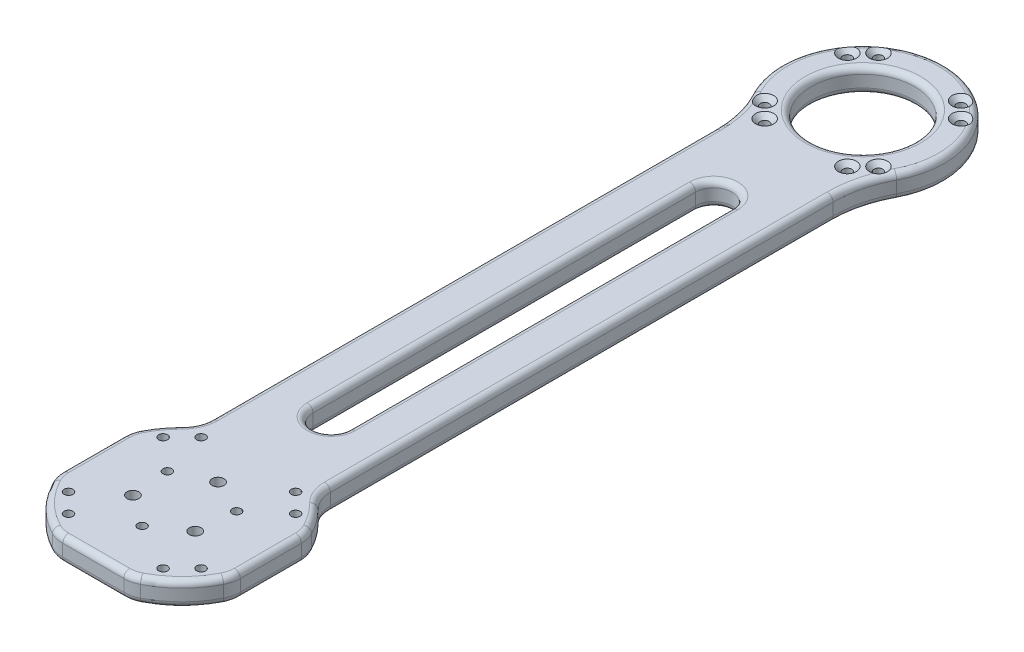
SolidWorks part; units mm, degrees
ref_plane "前视基准面" through (0, 0, 0) normal (0, 0, 1) x (1, 0, 0)
ref_plane "上视基准面" through (0, 0, 0) normal (0, 1, 0) x (1, 0, 0)
ref_plane "右视基准面" through (0, 0, 0) normal (1, 0, 0) x (0, 0, -1)
sketch "草图1" plane through (0, 0, 0) normal (0, 1, 0) x (1, 0, 0)
  line L0 (0, -31.6456) -> (0, -164.4547) construction
  line L2 (-30, 145) -> (-30, -145) construction
  line L3 (-30, -145) -> (30, -145) construction
  line L4 (30, 145) -> (30, -145) construction
  line L5 (-30, 145) -> (30, -145) construction
  line L6 (-30, -145) -> (30, 145) construction
  line L7 (-30, -85) -> (30, -85) construction
  line L8 (-30, -85) -> (-30, -145) construction
  line L9 (-30, -145) -> (30, -145) construction
  line L10 (30, -85) -> (30, -145) construction
  line L11 (-30, -85) -> (30, -145) construction
  line L12 (-30, -145) -> (30, -85) construction
  line L13 (-20, -84.896) -> (-20, 84.896)
  line L14 (-30, -104.6922) -> (-30, -125.3078)
  line L15 (-10.3078, -145) -> (10.3078, -145)
  line L16 (30, -104.6922) -> (30, -125.3078)
  line L17 (20, -84.896) -> (20, 84.896)
  line L18 (0, 0) -> (75.3378, 0) construction
  line L19 (0, -115) -> (-15.9693, -92.6118) construction
  line L20 (15.9693, -92.6118) -> (0, -115) construction
  line L21 (-30, 145) -> (30, 145) construction
  line L22 (0, 115) -> (39.9726, 115) construction
  line L23 (-19.2142, 128.9599) -> (0, 115) construction
  line L24 (-13.9599, 134.2142) -> (0, 115) construction
  circle A0 centre (0, -115) radius 32.5 construction
  arc A1 (-22.9412, -91.9793) -> (-28.8889, -100.111) centre (0, -115) ccw
  arc A2 (-28.8889, -129.889) -> (-14.889, -143.8889) centre (0, -115) ccw
  arc A3 (14.889, -143.8889) -> (28.8889, -129.889) centre (0, -115) ccw
  arc A4 (22.9412, -91.9793) -> (28.8889, -100.111) centre (0, -115) cw
  circle A5 centre (0, -115) radius 27.5 construction
  circle A6 centre (-15.9693, -92.6118) radius 1.5
  circle A8 centre (15.9693, -92.6118) radius 1.5
  circle A9 centre (-22.3882, -130.9693) radius 1.5
  circle A10 centre (-22.3882, -99.0307) radius 1.5
  circle A11 centre (-15.9693, -137.3882) radius 1.5
  circle A12 centre (15.9693, -137.3882) radius 1.5
  circle A13 centre (22.3882, -130.9693) radius 1.5
  circle A14 centre (22.3882, -99.0307) radius 1.5
  arc A15 (20, -84.896) -> (22.9412, -91.9793) centre (30, -84.896) ccw
  arc A16 (30, -104.6922) -> (28.8889, -100.111) centre (20, -104.6922) ccw
  arc A17 (28.8889, -129.889) -> (30, -125.3078) centre (20, -125.3078) ccw
  arc A18 (10.3078, -145) -> (14.889, -143.8889) centre (10.3078, -135) ccw
  arc A19 (-14.889, -143.8889) -> (-10.3078, -145) centre (-10.3078, -135) ccw
  arc A20 (-30, -125.3078) -> (-28.8889, -129.889) centre (-20, -125.3078) ccw
  arc A21 (-28.8889, -100.111) -> (-30, -104.6922) centre (-20, -104.6922) ccw
  arc A22 (-20, -84.896) -> (-22.9412, -91.9793) centre (-30, -84.896) cw
  circle A23 centre (0, -115) radius 13.5 construction
  circle A24 centre (0, -115) radius 12.15 construction
  circle A25 centre (0, -102.85) radius 2
  circle A27 centre (10.5222, -121.075) radius 2
  circle A28 centre (-10.5222, -121.075) radius 2
  circle A29 centre (0, -128.5) radius 1.5
  circle A30 centre (-11.6913, -108.25) radius 1.5
  circle A31 centre (11.6913, -108.25) radius 1.5
  circle A34 centre (0, 115) radius 23.75 construction
  circle A62 centre (0, 115) radius 17.5
  circle A63 centre (-19.2142, 128.9599) radius 1.5
  circle A64 centre (-13.9599, 134.2142) radius 1.5
  circle A65 centre (13.9599, 134.2142) radius 1.5
  circle A66 centre (19.2142, 128.9599) radius 1.5
  circle A67 centre (-19.2142, 101.0401) radius 1.5
  circle A68 centre (-13.9599, 95.7858) radius 1.5
  circle A69 centre (13.9599, 95.7858) radius 1.5
  circle A70 centre (19.2142, 101.0401) radius 1.5
  circle A71 centre (0, 115) radius 27.5 construction
  arc A72 (-24.2857, 102.0983) -> (24.2857, 102.0983) centre (0, 115) cw
  arc A73 (-24.2857, 102.0983) -> (-20, 84.896) centre (-56.6667, 84.896) cw
  arc A74 (24.2857, 102.0983) -> (20, 84.896) centre (56.6667, 84.896) ccw
  point P0 (0, 0)
  point P6 (0, -115)
  point P48 (22.981, -92.019)
  point P51 (30, -102.5)
  point P54 (30, -127.5)
  point P57 (12.5, -145)
  point P60 (-12.5, -145)
  point P63 (-30, -127.5)
  point P66 (-30, -102.5)
  point P69 (-22.981, -92.019)
  point P80 (0, -115)
  point P83 (20, 0)
  point P88 (0, -115)
  point P89 (-20, 0)
  dimension "D2" = 65
  dimension "D3" = 3
  dimension "D6" = 10
  dimension "D7" = 27
  dimension "D8" = 24.3
  dimension "D10" = 4
  dimension "D12" = 3
  dimension "D13" = 35
  dimension "D15" = 55
  dimension "D18" = 47.5
  dimension "D19" = 3
  dimension "D22" = 55
  dimension "D1" = 60
  dimension "D4" = 35.5
  dimension "D5" = 35.5
  dimension "D14" = 230
  dimension "D16" = 40
  dimension "D17" = 20
  dimension "D20" = 36
  dimension "D21" = 36
  dimension "D9" = 3
  dimension "D11" = 3
extrude "凸台-拉伸1" add sketch "草图1" along normal blind 8
fillet "圆角1" radius 2 22 edges at (-21.0876, 8, -93.7601) (0, 8, -142.5) (20, 8, 0) (20.7645, 8, 88.7308) (26.232, 8, 95.8133) (29.7183, 8, 102.3352) (30, 8, 115) (29.7183, 8, 127.6648) (22.981, 8, 137.981) (12.6648, 8, 144.7183) (0, 8, 145) (-12.6648, 8, 144.7183) (-22.981, 8, 137.981) (-29.7183, 8, 127.6648) (-30, 8, 115) (-29.7183, 8, 102.3352) (-26.232, 8, 95.8133) (-20.7645, 8, 88.7308) (-20, 8, 0) (0, 8, -97.5) (0, 0, -97.5) (21.0876, 8, -93.7601)
sketch "草图2" plane through (0, 0, 0) normal (0, -1, 0) x (1, 0, 0)
  line L0 (0, 64.6005) -> (0, -64.6005) construction
  line L1 (6.1519, 64.6005) -> (6.1519, -64.6005)
  line L2 (-6.1519, 64.6005) -> (-6.1519, -64.6005)
  arc A0 (6.1519, 64.6005) -> (-6.1519, 64.6005) centre (0, 64.6005) ccw
  arc A1 (-6.1519, -64.6005) -> (6.1519, -64.6005) centre (0, -64.6005) ccw
  point P2 (0, 0)
extrude "切除-拉伸1" cut sketch "草图2" against normal blind 21.5 and the other way blind 18
fillet "圆角2" radius 2 28 edges at (0, 8, -70.7524) (-6.1519, 8, 0) (0, 8, 70.7524) (0, 0, -70.7524) (-6.1519, 0, 0) (0, 0, 70.7524) (-21.0876, 0, -93.7601) (0, 0, -142.5) (20, 0, 0) (20.7645, 0, 88.7308) (26.232, 0, 95.8133) (29.7183, 0, 102.3352) (30, 0, 115) (29.7183, 0, 127.6648) (22.981, 0, 137.981) (12.6648, 0, 144.7183) (0, 0, 145) (-12.6648, 0, 144.7183) (-22.981, 0, 137.981) (-29.7183, 0, 127.6648) (-30, 0, 115) (-29.7183, 0, 102.3352) (-26.232, 0, 95.8133) (-20.7645, 0, 88.7308) (6.1519, 8, 0) (6.1519, 0, 0) (-20, 0, 0) (21.0876, 0, -93.7601)
chamfer "倒角1" distance 1.55 angle 45 8 edges at (13.9599, 8, -135.7142) (19.2142, 8, -130.4599) (19.2142, 8, -99.5401) (13.9599, 8, -94.2858) (-13.9599, 8, -97.2858) (-19.2142, 8, -102.5401) (-19.2142, 8, -127.4599) (-13.9599, 8, -132.7142)
